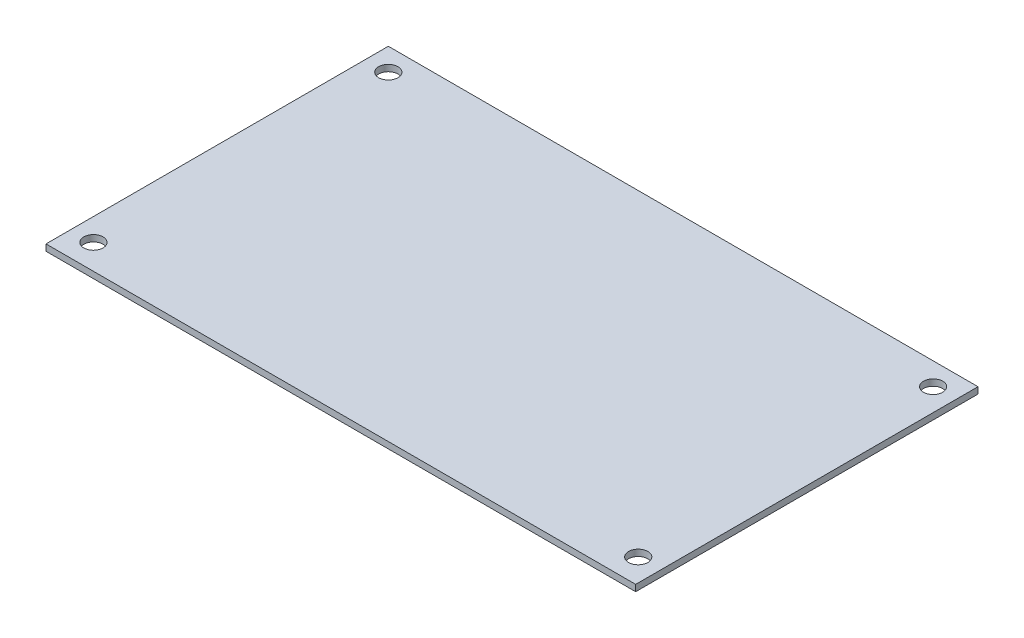
SolidWorks part; units mm, degrees
ref_plane "Спереди" through (0, 0, 0) normal (0, 0, 1) x (1, 0, 0)
ref_plane "Сверху" through (0, 0, 0) normal (0, 1, 0) x (1, 0, 0)
ref_plane "Справа" through (0, 0, 0) normal (1, 0, 0) x (0, 0, -1)
sketch "Эскиз1" plane through (0, 0, 0) normal (0, 1, 0) x (1, 0, 0)
  line L0 (-1000, 0) -> (49000, 0) construction
  line L1 (0, -1000) -> (0, 49000) construction
  line L2 (46, -1000) -> (46, 49000) construction
  line L3 (-46, -1000) -> (-46, 49000) construction
  line L4 (-1000, -26.705) -> (49000, -26.705) construction
  line L5 (-1000, 26.705) -> (49000, 26.705) construction
  line L6 (-46, 26.705) -> (-46, -26.705)
  line L7 (-46, -26.705) -> (46, -26.705)
  line L8 (46, -26.705) -> (46, 26.705)
  line L9 (46, 26.705) -> (-46, 26.705)
  dimension "D1" = 46
  dimension "D2" = 46
  dimension "D3" = 26.705
  dimension "D4" = 26.705
extrude "Бобышка-Вытянуть1" add sketch "Эскиз1" along normal blind 1
sketch "Эскиз2" plane through (0, 1, 0) normal (0, 1, 0) x (1, 0, 0)
  line L0 (-1000, 0) -> (49000, 0) construction
  line L1 (0, -1000) -> (0, 49000) construction
  line L2 (-1056.6326, -22.805) -> (48943.3674, -22.805) construction
  line L3 (-1000, 23.205) -> (49000, 23) construction
  line L4 (42.5, -1000) -> (42.5, 49000) construction
  line L5 (-42.5, -1000) -> (-42.5, 49000) construction
  line L6 (-1035.3555, -26.705) -> (48964.6445, -26.705) construction
  line L8 (-1036.0545, 26.705) -> (48963.9455, 26.705) construction
  circle A0 centre (-42.5, 23.2011) radius 1.5
  circle A1 centre (42.5, 23.2007) radius 1.5
  circle A4 centre (-42.5, -22.805) radius 1.5
  circle A5 centre (42.5, -22.805) radius 1.5
  dimension "D3" = 42.5
  dimension "D4" = 42.5
extrude "Вырез-Вытянуть1" cut sketch "Эскиз2" against normal blind 10
